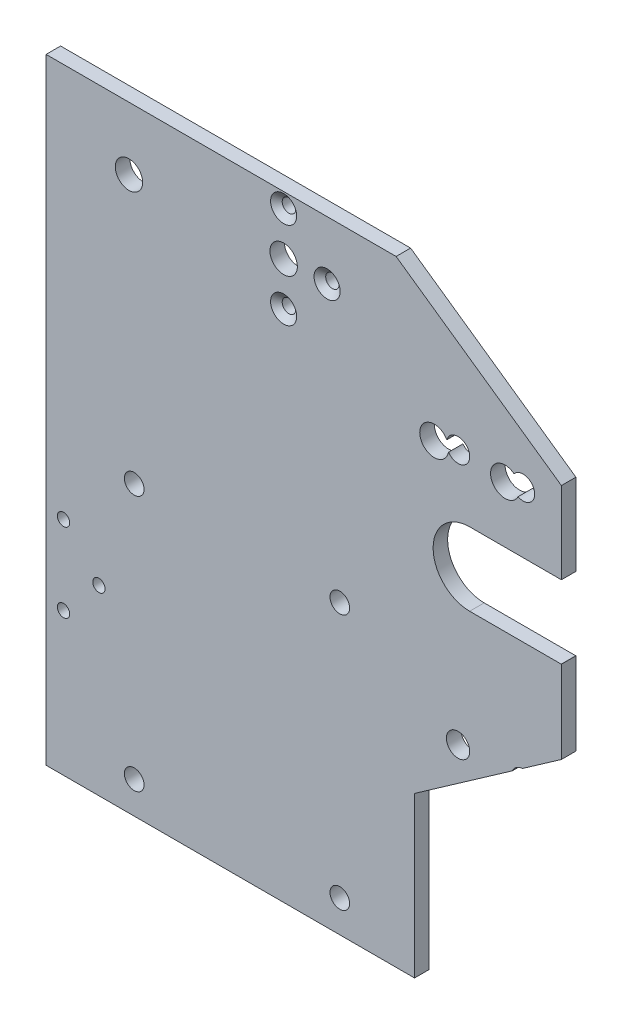
SolidWorks part; units mm, degrees
note: '?' marks a value the reader was unsure of.
material "5052-H32"
ref_plane "Front" through (0, 0, 0) normal (0, 0, 1) x (1, 0, 0)
ref_plane "Top" through (0, 0, 0) normal (0, 1, 0) x (1, 0, 0)
ref_plane "Right" through (0, 0, 0) normal (1, 0, 0) x (0, 0, -1)
ref_axis "side-side" through (80.9, 0, 0) along (-1, 0, 0)?
ref_axis "up-down" through (0, 50, 0) along (0, -1, 0)?
ref_axis "front-back" through (0, 0, -80.9) along (0, 0, 1)?
sketch3d "3DSketch1"
  line L1 (-36.063, 17.578, 17.275) -> (-36.063, -7.822, 17.275)
  line L3 (-32.888, 17.578, 14.1) -> (-32.888, -7.822, 14.1)
  line L8 (27.5, 33, 11.8) -> (-27.5, 33, 11.8)
  line L9 (-27.5, 33, 11.8) -> (-27.5, -33, 11.8)
  line L10 (-27.5, -33, 11.8) -> (27.5, -33, 11.8)
  line L11 (27.5, -33, 11.8) -> (27.5, 33, 11.8)
  line L20 (12.852, 79.3579, 11.8) -> (17.9378, 74.2721, 11.8)
  line L21 (17.9378, 74.2721, 11.8) -> (20.7662, 74.2721, 11.8)
  line L22 (20.7662, 74.2721, 11.8) -> (32.0799, 85.5858, 11.8)
  line L23 (32.0799, 85.5858, 11.8) -> (32.0799, 88.4142, 11.8)
  line L24 (32.0799, 88.4142, 11.8) -> (20.7662, 99.7279, 11.8)
  line L25 (20.7662, 99.7279, 11.8) -> (17.9378, 99.7279, 11.8)
  line L26 (17.9378, 99.7279, 11.8) -> (12.852, 94.6421, 11.8)
  line L27 (12.852, 94.6421, 11.8) -> (12.852, 79.3579, 11.8)
  circle A1 centre (-13.356, 28, 11.8) radius 2.025
  circle A2 centre (-51.308, -14.6, 8.382) radius 19.2253 construction
  circle A3 centre (-55.372, 23.5, 14.3256) radius 19.2278 construction
  circle A4 centre (60.066, 41.6513, -10.821) radius 18.5
  circle A5 centre (67.816, 55.0747, -10.821) radius 1.25
  circle A7 centre (52.316, 28.2279, -14.321) radius 1.25
  circle A8 centre (-22.5, 28, 11.8) radius 2.025
  circle A9 centre (22.5, 28, 11.8) radius 2.025
  circle A10 centre (22.5, -28, 11.8) radius 2.025
  circle A11 centre (-22.5, -28, 11.8) radius 2.025
  circle A13 centre (67.816, 28.2279, -14.321) radius 1.25
  circle A15 centre (44.566, 41.6513, -10.821) radius 1.25
  circle A18 centre (75.566, 41.6513, -10.821) radius 1.25
  circle A20 centre (52.316, 55.0747, -10.821) radius 1.25
  circle A21 centre (31.644, -28, 11.8) radius 2.025
  circle A22 centre (19.352, 96.5191, 11.8) radius 1.1303
  circle A24 centre (19.352, 77.4809, 11.8) radius 1.1303
  circle A26 centre (22.352, 87, 23.5) radius 6
  circle A27 centre (22.352, 87, 23.5) radius 3
  circle A28 centre (28.8711, 87, 11.8) radius 1.1303
  circle A29 centre (22.352, 87, 31.5) radius 3
  circle A31 centre (22.352, 87, 31.5) radius 3.8268
  circle A33 centre (22.352, 87, 30.85) radius 4.5
  arc A40 (-37.9129, 67.2371, 9.4869) -> (-37.9129, 62.5513, 9.4869) centre (-46.0199, 64.8942, 9.4869) ccw
  arc A41 (-37.9129, 62.5513, 9.4869) -> (-32.1541, 62.5513, 9.4869) centre (-35.0335, 61.7192, 9.4869) ccw
  arc A42 (-32.1541, 62.5513, 9.4869) -> (-32.1541, 67.2371, 9.4869) centre (-24.0471, 64.8942, 9.4869) ccw
  arc A43 (-32.1541, 67.2371, 9.4869) -> (-37.9129, 67.2371, 9.4869) centre (-35.0335, 68.0692, 9.4869) ccw
  point P16 (31.644, -28, 13.825)
  point P21 (-22.5, 28, 13.825)
  point P23 (22.5, 28, 13.825)
  point P25 (22.5, -28, 13.825)
  point P27 (-22.5, -28, 13.825)
  point P33 (44.566, 41.6513, -12.071)
  point P37 (19.352, 96.5191, 12.9303)
  point P42 (19.352, 77.4809, 12.9303)
  point P48 (28.8711, 87, 12.9303)
  point P50 (-51.308, -14.6, 27.6073)
  point P51 (-13.356, 28, 13.825)
  point P58 (-55.372, 23.5, -4.9022)
  point P60 (22.352, 87, 17.5)
  point P62 (22.352, 87, 26.5)
  point P67 (22.352, 87, 28.5)
  point P71 (22.352, 87, 35.3268)
  point P76 (22.352, 87, 35.35)
  point P78 (-46.0199, 64.8942, 1.0482)
  point P80 (-35.0335, 61.7192, 12.4841)
  point P81 (-24.0471, 64.8942, 1.0482)
  point P83 (-35.0335, 68.0692, 12.4841)
  point P85 (52.316, 55.0747, -12.071)
  point P100 (60.066, 41.6513, -29.321)
  point P103 (67.816, 55.0747, -12.071)
  point P116 (52.316, 28.2279, -13.071)
  point P128 (67.816, 28.2279, -13.071)
  point P133 (75.566, 41.6513, -12.071)
sketch "Sketch1" plane through (0, 0, 0) normal (0, 1, 0) x (1, 0, 0)
  line L0 (-32.638, -14.975) -> (80.144, -14.975)
  line L1 (49.144, -9.3) -> (49.144, -0.5) construction
  line L7 (80.144, -14.975) -> (80.144, -11.8)
  line L8 (80.144, -11.8) -> (-32.638, -11.8)
  line L9 (-32.638, -11.8) -> (-32.638, -14.975)
  line L10 (27.5, -11.8) -> (-27.5, -11.8) construction
  line L11 (0, -50) -> (0, 50) construction
  line L13 (-38.0307, -1.4658) -> (-38.0307, -18.0357) construction
  dimension "D1" = 3.175
  dimension "D2" = 31
  dimension "D3" = 0.25
  dimension "D5" = 5.138
  dimension "D6" = 80.144
extrude "Boss-Extrude1" add sketch "Sketch1" along normal blind 99.75 and the other way blind 35
sketch "Sketch2" plane through (0, 0, 0) normal (0, 0, 1) x (1, 0, 0)
  line L0 (60.066, 48.5504) -> (80.066, 48.5504) construction
  line L1 (48, -35) -> (80.144, -35)
  line L2 (48, -35) -> (48, -0.0202)
  line L3 (60.066, 56.5504) -> (80.066, 56.5504)
  line L4 (80.144, -35) -> (80.144, 22.4873)
  line L5 (43.9647, 99.75) -> (80.144, 74.417)
  line L6 (43.9647, 99.75) -> (80.144, 99.75)
  line L7 (60.066, 40.5504) -> (80.066, 40.5504)
  line L9 (80.144, 99.75) -> (80.144, 74.417)
  line L10 (80.144, 22.4873) -> (48, -0.0202)
  line L11 (0, -50) -> (0, 50) construction
  line L12 (-32.638, -35) -> (80.144, -35) construction
  line L13 (-32.638, 99.75) -> (80.144, 99.75) construction
  arc A0 (60.066, 56.5504) -> (60.066, 40.5504) centre (60.066, 48.5504) ccw
  arc A1 (80.066, 40.5504) -> (80.066, 56.5504) centre (80.066, 48.5504) ccw
  circle A2 centre (67.816, 68.9738) radius 3.175
  circle A3 centre (52.316, 68.9738) radius 3.175
  point P1 (70.066, 48.5504)
  dimension "D9" = 6.35
  dimension "D1" = 48
  dimension "D2" = 38.6
  dimension "D3" = 55
  dimension "D4" = 55
  dimension "D5" = 16
  dimension "D6" = 20
  dimension "D7" = 32.144
  dimension "D8" = 38.6866
  dimension "D10" = 43.9647
extrude "Cut-Extrude1" cut sketch "Sketch2" against normal through all and the other way through all
sketch "Sketch3" [suppressed] plane through (43.8, 0, 0) normal (1, 0, 0) x (0, 0, -1)
  line L0 (-11.8, -12.8411) -> (-14.1, -12.8411) construction
  line L1 (10.819, 98) -> (2.819, 98)
  line L2 (10.819, 98) -> (10.819, 71.012)
  line L3 (10.819, 71.012) -> (2.819, 71.012)
  line L4 (2.819, 98) -> (2.819, 71.012)
  line L5 (10.819, -35) -> (2.819, -35)
  line L6 (10.819, -35) -> (10.819, -12.8411)
  line L7 (10.819, -12.8411) -> (2.819, -12.8411)
  line L8 (2.819, -35) -> (2.819, -12.8411)
  dimension "D1" = 8
  dimension "D2" = 8
extrude "Cut-Extrude2" [suppressed] cut sketch "Sketch3" against normal blind 3
hole_wizard "M4 Clearance Hole1" positions "Sketch4" profile "Sketch5" hole size "M4" standard "ANSI Metric" end condition through all
sketch "Sketch4" plane through (0, 0, 14.975) normal (0, 0, 1) x (1, 0, 0)
  point P0 (-13.356, 28)
  point P3 (31.644, 28)
  point P6 (31.644, -28)
  point P9 (-13.356, -28)
sketch "Sketch5" plane through (-13.356, 28, 14.975) normal (1, 0, 0) x (0, -1, 0)
  line L0 (0, 0) -> (0, 3.175)
  line L1 (0, 3.175) -> (2.15, 3.175)
  line L2 (2.15, 3.175) -> (2.15, 0)
  line L5 (2.15, 0) -> (0, 0)
  line L11 (0, -6.35) -> (0, 107.95) construction
  dimension "Thru Hole Dia." = 4.3
  dimension "Thru Hole Depth" = 3.175
hole_wizard "CSK for #4 Flat Head Machine Screw (100)1" positions "Sketch6" profile "Sketch7" countersink size "#4" standard "ANSI Inch" end condition through all
sketch "Sketch6" plane through (0, 0, 14.975) normal (0, 0, 1) x (1, 0, 0)
  point P70 (19.352, 96.5191)
  point P73 (28.8711, 87)
  point P76 (19.352, 77.4809)
sketch "Sketch7" plane through (19.352, 96.5191, 14.975) normal (1, 0, 0) x (0, -1, 0)
  line L0 (0, 0) -> (0, 3.175)
  line L1 (0, 3.175) -> (1.4732, 3.175)
  line L2 (1.4732, 3.175) -> (1.4732, 1.1616)
  line L3 (1.4732, 1.1616) -> (2.8575, 0)
  line L5 (2.8575, 0) -> (0, 0)
  line L6 (-1.4732, 1.1616) -> (-2.8575, 0) construction
  line L11 (0, -6.35) -> (0, 107.95) construction
  dimension "Thru Hole Dia." = 2.9464
  dimension "Thru Hole Depth" = 3.175
  dimension "Near C'Sink Dia." = 5.715
  dimension "Near C'Sink Angle" = 100
sketch "Sketch8" plane through (0, 0, 14.975) normal (0, 0, 1) x (1, 0, 0)
  circle A1 centre (19.352, 87) radius 3
  dimension "D1" = 6
extrude "Cut-Extrude3" cut sketch "Sketch8" against normal blind 3.5
hole_wizard "5/16-18 Tapped Hole1" [suppressed] positions "Sketch9" profile "Sketch10" tap size "5/16-18" standard "ANSI Inch"
sketch "Sketch9" plane through (0, 0, 14.975) normal (0, 0, 1) x (1, 0, 0)
  point P0 (-12.7036, 77.5964)
sketch "Sketch10" plane through (-12.7036, 77.5964, 14.975) normal (1, 0, 0) x (0, -1, 0)
  line L0 (0, 0) -> (0, 3.175)
  line L1 (0, 3.175) -> (3.2639, 3.175)
  line L2 (3.2639, 3.175) -> (3.2639, 0)
  line L5 (3.2639, 0) -> (0, 0)
  line L11 (0, -6.35) -> (0, 107.95) construction
  dimension "Thread Major Dia." = 6.5278
  dimension "Thru Tap Drill Depth" = 3.175
hole_wizard "#6-32 Tapped Hole1" positions "Sketch12" profile "Sketch13" tap size "#6-32" standard "ANSI Inch" end condition through all
sketch "Sketch12" plane through (0, 0, 14.975) normal (0, 0, 1) x (1, 0, 0)
  point P0 (-28.824, -3.758)
  point P3 (-21.077, 4.878)
  point P6 (-28.824, 13.514)
sketch "Sketch13" plane through (-28.824, -3.758, 14.975) normal (1, 0, 0) x (0, -1, 0)
  line L0 (0, 0) -> (0, 3.175)
  line L1 (0, 3.175) -> (1.3525, 3.175)
  line L2 (1.3525, 3.175) -> (1.3525, 0)
  line L5 (1.3525, 0) -> (0, 0)
  line L11 (0, -6.35) -> (0, 107.95) construction
  dimension "Thread Major Dia." = 2.7051
  dimension "Thru Tap Drill Depth" = 3.175
hole_wizard "1/4-20 Tapped Hole1" positions "Sketch14" profile "Sketch15" tap size "1/4-20" standard "ANSI Inch" end condition through all
sketch "Sketch14" plane through (0, 0, 14.975) normal (0, 0, 1) x (1, 0, 0)
  point P0 (57.526, 13.97)
  point P3 (71.75, 13.97)
  point P6 (71.75, 69.85)
  point P9 (57.526, 69.85)
sketch "Sketch15" plane through (57.526, 13.97, 14.975) normal (1, 0, 0) x (0, -1, 0)
  line L0 (0, 0) -> (0, 3.175)
  line L1 (0, 3.175) -> (2.5527, 3.175)
  line L2 (2.5527, 3.175) -> (2.5527, 0)
  line L5 (2.5527, 0) -> (0, 0)
  line L11 (0, -6.35) -> (0, 107.95) construction
  dimension "Thread Major Dia." = 5.1054
  dimension "Thru Tap Drill Depth" = 3.175
sketch "Sketch16" plane through (0, 0, 14.975) normal (0, 0, 1) x (1, 0, 0)
  line L1 (-20.8561, -40) -> (-20.8561, 370.2) construction
  line L2 (-32.638, -35) -> (-32.638, 99.75) construction
  line L3 (-32.638, 99.75) -> (43.9647, 99.75) construction
  circle A0 centre (-14.5061, 86.034) radius 2.9972
  circle A1 centre (19.352, 87) radius 3 construction
  dimension "D1" = 6.35
  dimension "D2" = 33.8581
  dimension "D3" = 18.1319
  dimension "D5" = 5.9944
  dimension "D4" = 13.716
extrude "Cut-Extrude4" cut sketch "Sketch16" against normal through all
